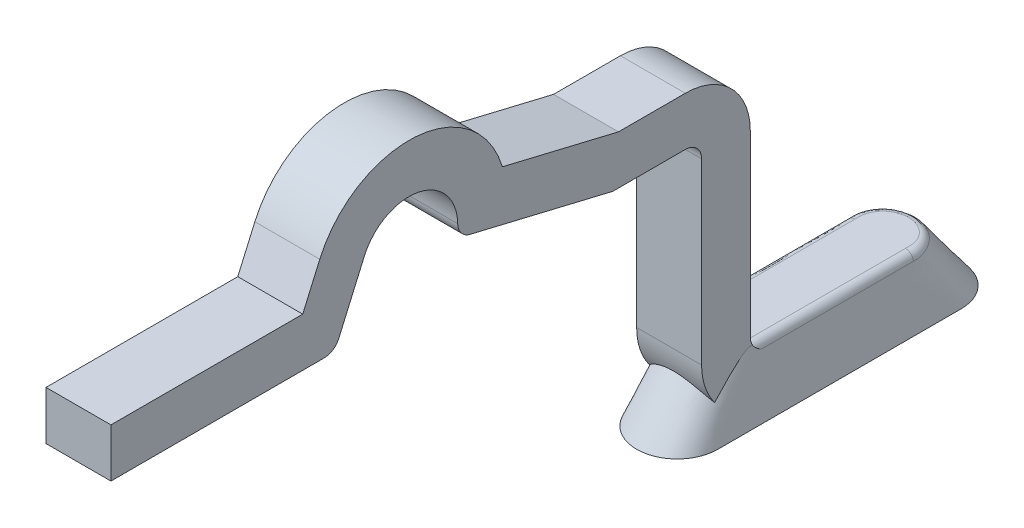
SolidWorks part; units mm, degrees
material "Pure Gold"
ref_plane "Front Plane" through (0, 0, 0) normal (0, 0, 1) x (1, 0, 0)
ref_plane "Top Plane" through (0, 0, 0) normal (0, 1, 0) x (1, 0, 0)
ref_plane "Right Plane" through (0, 0, 0) normal (1, 0, 0) x (0, 0, -1)
ref_plane "Plane1" through (0, -0.05, 0) normal (0, 1, 0) x (1, 0, 0)
sketch "Sketch1" plane through (0, 0, 0) normal (1, 0, 0) x (0, 0, -1)
  line L0 (1, 0) -> (0.4, 0)
  line L1 (0.2778, 0) -> (-0.2778, 0) construction
  line L2 (0, 0.4) -> (0, 1.5)
  line L3 (0, 0.2778) -> (0, -0.2778) construction
  line L4 (-0.1, 1.6) -> (-0.5473, 1.6)
  line L5 (-0.5473, 1.6) -> (-1.4258, 1.81)
  line L6 (-2.0774, 2.0202) -> (-2.2349, 1.6599)
  line L7 (-2.3265, 1.6) -> (-3.6389, 1.6)
  arc A0 (0.4, 0) -> (0, 0.4) centre (0.4, 0.4) cw
  arc A1 (0, 1.5) -> (-0.1, 1.6) centre (-0.1, 1.5) ccw
  arc A2 (-1.5026, 1.9054) -> (-2.0774, 2.0202) centre (-1.8025, 1.9) ccw
  arc A3 (-1.4258, 1.81) -> (-1.5026, 1.9054) centre (-1.4026, 1.9072) cw
  arc A4 (-2.2349, 1.6599) -> (-2.3265, 1.6) centre (-2.3265, 1.7) cw
  point P11 (0, 0)
  point P14 (0, 1.6)
  dimension "D3" = 0.4
  dimension "D4" = 0.1
  dimension "D6" = 0.1
  dimension "D7" = 0.1
  dimension "D9" = 0.3
  dimension "D1" = 1.6
  dimension "D2" = 1
  dimension "D12" = 0
  dimension "D13" = 0.3
extrude "Extrude-Thin1" add sketch "Sketch1" along normal mid plane 0.4 thin
sketch "Sketch2" plane through (0, -0.05, 0) normal (0, 1, 0) x (1, 0, 0)
  line L0 (0, 1.55) -> (0, 0.05) construction
  line L1 (0, -1.7919) -> (0, 1.7919) construction
  line L2 (0.25, 1.55) -> (0.25, 0.05)
  line L3 (-0.25, 1.55) -> (-0.25, 0.05)
  line L4 (-0.2802, 0) -> (0.2802, 0) construction
  arc A0 (0.25, 1.55) -> (-0.25, 1.55) centre (0, 1.55) ccw
  arc A1 (-0.25, 0.05) -> (0.25, 0.05) centre (0, 0.05) ccw
  point P5 (0, 0.8)
  dimension "D1" = 0.5
  dimension "D2" = 0.8
  dimension "D3" = 1.5
ref_plane "Plane2" through (0, 0.35, 0) normal (0, 1, 0) x (1, 0, 0)
sketch "Sketch3" plane through (0, 0.35, 0) normal (0, 1, 0) x (1, 0, 0)
  line L0 (0, 1.3) -> (0, 0.3) construction
  line L1 (0, 1.55) -> (0, 0.05) construction
  line L2 (0.2, 1.3) -> (0.2, 0.3)
  line L3 (-0.2, 1.3) -> (-0.2, 0.3)
  line L4 (-0.28, 0) -> (0.28, 0) construction
  arc A0 (0.2, 1.3) -> (-0.2, 1.3) centre (0, 1.3) ccw
  arc A1 (-0.2, 0.3) -> (0.2, 0.3) centre (0, 0.3) ccw
  point P4 (0, 0.8)
  dimension "D2" = 0.2
  dimension "D1" = 1
  dimension "D3" = 0.8
loft "Loft1" add profiles "Sketch3", "Sketch2"
fillet "Fillet2" radius 0.05 4 edges
